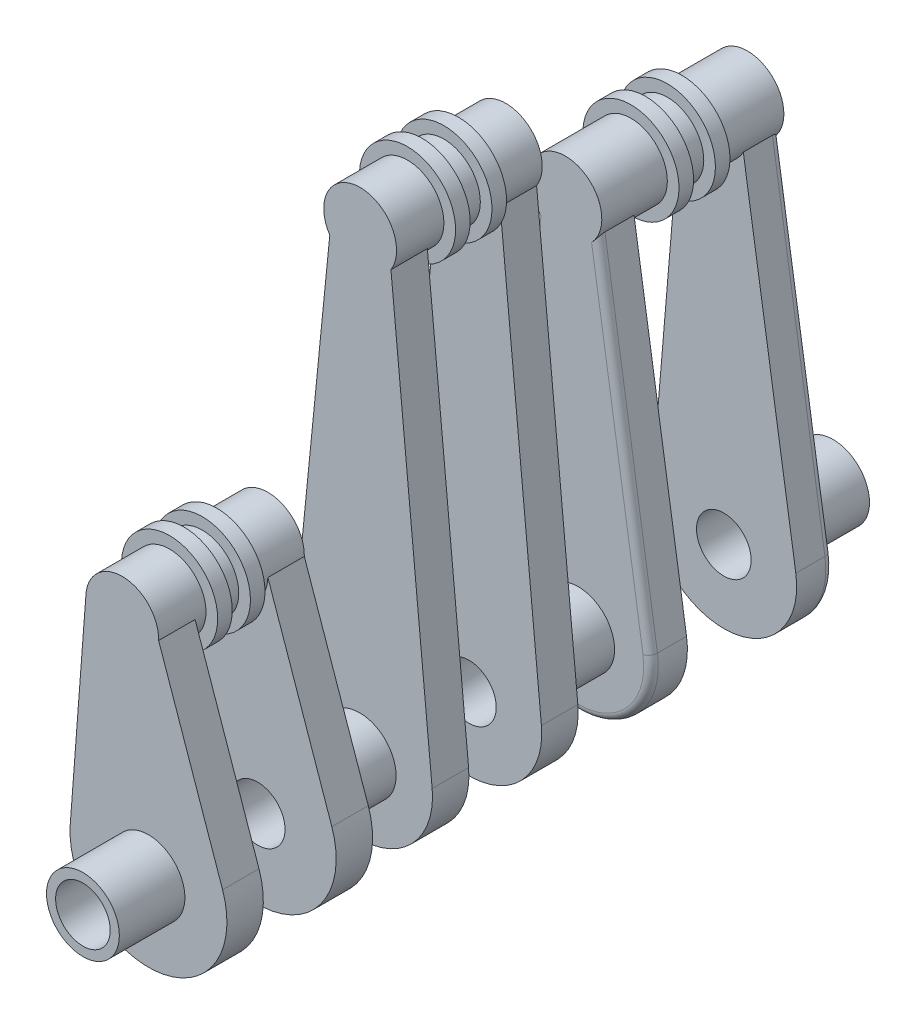
SolidWorks part; units mm, degrees
material "Ferro fundido maleável"
ref_plane "Plano frontal" through (0, 0, 0) normal (0, 0, 1) x (1, 0, 0)
ref_plane "Plano superior" through (0, 0, 0) normal (0, 1, 0) x (1, 0, 0)
ref_plane "Plano direito" through (0, 0, 0) normal (1, 0, 0) x (0, 0, -1)
sketch "Esboço1" plane through (0, 0, 0) normal (0, 0, 1) x (1, 0, 0)
  circle A0 centre (0, 0) radius 10
  dimension "D1" = 20
extrude "Ressalto-extrusão1" add sketch "Esboço1" along normal blind 20
sketch "Esboço2" plane through (0, 0, 20) normal (0, 0, 1) x (0.9994, 0.0349, 0)
  line L2 (-8.6928, 95.7568) -> (-19.8585, 2.3745)
  line L3 (8.6928, 95.7568) -> (19.8585, 2.3745)
  arc A6 (-19.8585, 2.3745) -> (19.8585, 2.3745) centre (0, 0) ccw
  arc A11 (8.6928, 95.7568) -> (-8.6928, 95.7568) centre (0, 100.7) ccw
  dimension "D1" = 20
  dimension "D2" = 40
  dimension "D3" = 100.7
extrude "Ressalto-extrusão2" add sketch "Esboço2" along normal blind 10
fillet "Filete1" radius 2 3 edges at (0.698, -19.9878, 20) (-15.9793, 48.5375, 20) (12.5546, 49.534, 20)
sketch "Esboço3" plane through (0, 0, 30) normal (0, 0, 1) x (1, 0, 0)
  circle A0 centre (-3.5144, 100.6387) radius 10
  arc A1 (5.3457, 96.0019) -> (-12.0294, 95.3951) centre (-3.5144, 100.6387) ccw construction
  dimension "D1" = 0
extrude "Ressalto-extrusão3" add sketch "Esboço3" along normal blind 15
mirror "Espelhar1" about plane through (-3.5144, 100.6387, 45) normal (0, 0, 1) of bodies 103
sketch "Esboço4" plane through (0, 0, 90) normal (0, 0, 1) x (1, -0.001, 0)
  line L0 (-8.3351, 119.4749) -> (-19.9038, 1.9594)
  line L1 (8.4603, 119.6686) -> (19.9061, 1.9353)
  arc A0 (-19.9038, 1.9594) -> (19.9061, 1.9353) centre (0, 0) ccw
  arc A1 (8.4603, 119.6686) -> (-8.3351, 119.4749) centre (0, 125) ccw
  dimension "D1" = 20
  dimension "D2" = 40
  dimension "D3" = 125
extrude "Ressalto-extrusão4" add sketch "Esboço4" along normal blind 10
sketch "Esboço5" plane through (0, 0, 100) normal (0, 0, 1) x (1, 0, 0)
  circle A0 centre (0.1309, 124.9999) radius 10
  arc A1 (8.5856, 119.6597) -> (-8.21, 119.4836) centre (0.1309, 124.9999) ccw construction
  dimension "D1" = 0
extrude "Ressalto-extrusão5" add sketch "Esboço5" along normal blind 10
mirror "Espelhar2" about plane through (0.1309, 124.9999, 110) normal (0, 0, 1) of bodies 106
sketch "Esboço6" plane through (0, 0, 220) normal (0, 0, 1) x (1, 0, 0)
  line L1 (-29.904, -20.949) -> (32.449, -20.949)
  line L2 (-29.904, -20.949) -> (-29.904, 147.2022)
  line L3 (-29.904, 147.2022) -> (32.449, 147.2022)
  line L4 (32.449, -20.949) -> (32.449, 147.2022)
extrude "Corte-extrusão1" cut sketch "Esboço6" along direction (0, 0, 1) on the side against the normal blind 72
sketch "Esboço7" plane through (0, 0, 148) normal (0, 0, 1) x (-0.8952, 0.4456, 0)
  line L1 (41.2856, -44.3493) -> (19.9623, 8.1136)
  line L2 (23.1499, -52.781) -> (-15.0665, -15.4054)
  line L3 (0, 0) -> (32.2178, -48.5652) construction
  line L4 (32.2178, -48.5652) -> (77.1778, -116.3381) construction
  line L5 (55.5794, -111.964) -> (0, 0) construction
  arc A1 (19.9623, 8.1136) -> (-15.0665, -15.4054) centre (0, 0) ccw
  arc A6 (23.1499, -52.781) -> (41.2856, -44.3493) centre (32.2178, -48.5652) ccw
  dimension "D1" = 20
  dimension "D2" = 58.28
  dimension "D3" = 7.16
extrude "Ressalto-extrusão6" add sketch "Esboço7" along normal blind 10
sketch "Esboço13" plane through (0, 0, 158) normal (0, 0, 1) x (1, 0, 0)
  circle A0 centre (-7.2035, 57.8331) radius 10
extrude "Ressalto-extrusão10" add sketch "Esboço13" along normal blind 10
sketch "Esboço10" plane through (0, 0, 0) normal (0, 0, -1) x (-1, 0, 0)
  circle A0 centre (0, 0) radius 7.5
  dimension "D1" = 15
extrude "Corte-extrusão3" cut sketch "Esboço10" against normal through all
sketch "Esboço12" plane through (0, 0, 130) normal (0, 0, 1) x (1, 0, 0)
  circle A0 centre (0.1309, 124.9999) radius 13.2035
extrude "Ressalto-extrusão9" add sketch "Esboço12" along normal blind 4 from offset 27 offset against normal yes
sketch "Esboço14" plane through (0, 0, 130) normal (0, 0, 1) x (1, 0, 0)
  circle A0 centre (0.1309, 124.9999) radius 13.2035
extrude "Ressalto-extrusão11" add sketch "Esboço14" along normal blind 4 from offset 17 offset against normal yes
mirror "Espelhar3" about plane through (-7.2035, 57.8331, 168) normal (0, 0, 1) of bodies 119
sketch "Esboço15" plane through (0, 0, 336) normal (0, 0, 1) x (1, 0, 0)
  line L1 (-34.7822, -27.0803) -> (35.0204, -27.0803)
  line L2 (-34.7822, -27.0803) -> (-34.7822, 143.4998)
  line L3 (-34.7822, 143.4998) -> (35.0204, 143.4998)
  line L4 (35.0204, -27.0803) -> (35.0204, 143.4998)
extrude "Corte-extrusão4" cut sketch "Esboço15" against normal up to surface (130 mm away) up to face at (10, 0, 206)
sketch "Esboço16" plane through (0, 0, 188) normal (0, 0, 1) x (1, 0, 0)
  circle A1 centre (-7.2035, 57.8331) radius 13.205
extrude "Ressalto-extrusão12" add sketch "Esboço16" against normal blind 4 from offset 13 offset against normal yes
sketch "Esboço17" plane through (0, 0, 188) normal (0, 0, 1) x (1, 0, 0)
  circle A0 centre (-7.2035, 57.8331) radius 13.205
extrude "Ressalto-extrusão13" add sketch "Esboço17" against normal blind 4 from offset 22 offset against normal yes
sketch "Esboço18" plane through (0, 0, 70) normal (0, 0, 1) x (1, 0, 0)
  circle A1 centre (-3.5144, 100.6387) radius 13.205
extrude "Ressalto-extrusão14" add sketch "Esboço18" along normal blind 4 from offset 22 offset against normal yes
sketch "Esboço19" plane through (0, 0, 70) normal (0, 0, 1) x (1, 0, 0)
  circle A0 centre (-3.5144, 100.6387) radius 13.205
extrude "Ressalto-extrusão15" add sketch "Esboço19" along normal blind 4 from offset 32 offset against normal yes
